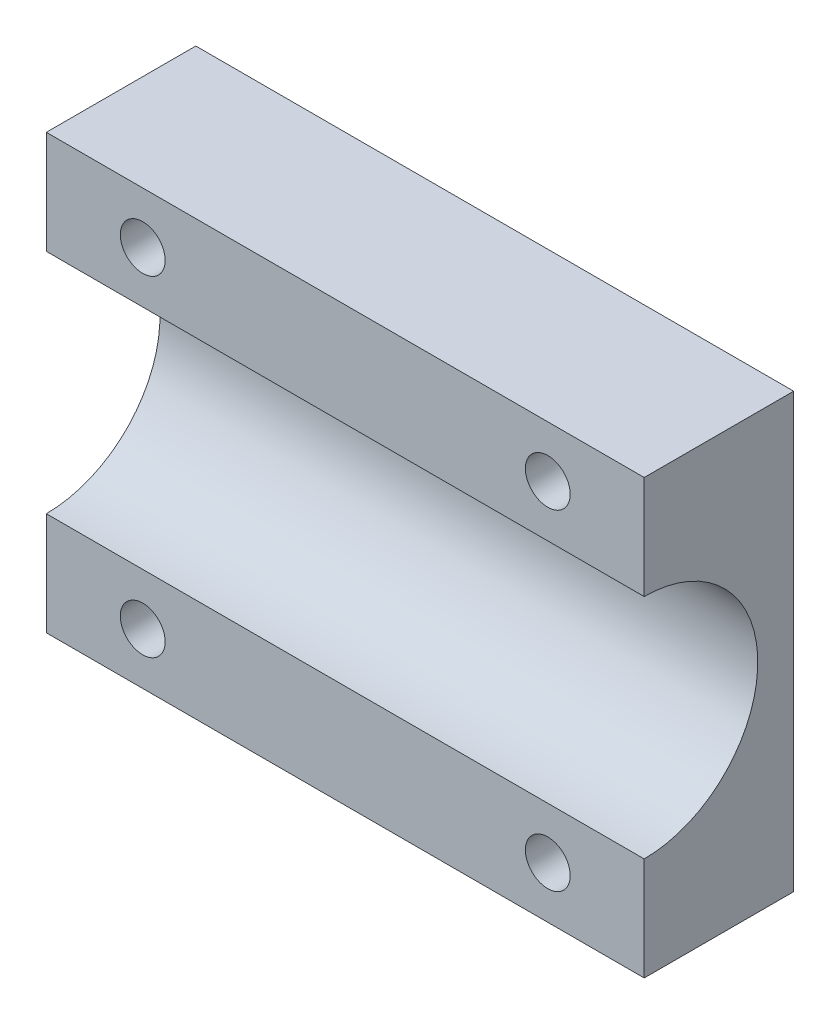
SolidWorks part; units mm, degrees
ref_plane "Front Plane" through (0, 0, 0) normal (1, 0, 0) x (0, 1, 0)
ref_plane "Top Plane" through (0, 0, 0) normal (0, 0, 1) x (0, 1, 0)
ref_plane "Right Plane" through (0, 0, 0) normal (0, 1, 0) x (-1, 0, 0)
sketch "Sketch1" plane through (0, 0, 0) normal (0, 0, 1) x (0, 1, 0)
  line L1 (0, 0) -> (29, 0)
  line L2 (0, 0) -> (0, -40)
  line L3 (0, -40) -> (29, -40)
  line L4 (29, 0) -> (29, -40)
  dimension "D1" = 29
  dimension "D2" = 40
extrude "Boss-Extrude1" add sketch "Sketch1" along normal blind 10 contours L4 L1 L2 L3 region at (20, 14.5, 0)
sketch "Sketch2" plane through (40, 0, 0) normal (1, 0, 0) x (0, 1, 0)
  line L0 (0, 10) -> (29, 10) construction
  circle A0 centre (14.5, 10) radius 7.6
  dimension "D1" = 15.2
extrude "Cut-Extrude1" cut sketch "Sketch2" against normal up to surface (40 mm away) up to face at (0, 14.5, 5)
sketch "Sketch3" plane through (0, 0, 10) normal (0, 0, 1) x (1, 0, 0)
  line L0 (0, 29) -> (12.9, 22.1) construction
  line L1 (40, 22.1) -> (0, 22.1) construction
  line L2 (0, 22.1) -> (12.9, 29) construction
  line L3 (0, 29) -> (40, 29) construction
  line L4 (40, 29) -> (27.1, 22.1) construction
  line L5 (40, 22.1) -> (27.1, 29) construction
  line L6 (0, 6.9) -> (12.9, 0) construction
  line L7 (0, 0) -> (40, 0) construction
  line L8 (0, 0) -> (12.9, 6.9) construction
  line L9 (0, 6.9) -> (40, 6.9) construction
  line L10 (40, 0) -> (27.1, 6.9) construction
  line L11 (40, 6.9) -> (27.1, 0) construction
  circle A0 centre (6.45, 25.55) radius 1.5
  circle A1 centre (33.55, 25.55) radius 1.5
  circle A2 centre (33.55, 3.45) radius 1.5
  circle A3 centre (6.45, 3.45) radius 1.5
  dimension "D2" = 12.9
  dimension "D3" = 12.9
extrude "Cut-Extrude2" cut sketch "Sketch3" against normal up to surface (10 mm away) up to face at (20, 14.5, 0)
equation "\"screw_hole\"= 3mm"
equation "\"offset\"= 2.52mm"
equation "\"y_length\" = 40mm"
equation "\"z_breadth\"= 29mm"
equation "\"D1@Sketch1\"=\"z_breadth\""
equation "\"D2@Sketch1\"=\"y_length\""
equation "\"lm8uu_bearing_dia\"= 15.2mm"
equation "\"D1@Sketch2\"=\"lm8uu_bearing_dia\""
equation "\"D1@Sketch3\"=\"screw_hole\""
equation "\"D3@Sketch3\"=\"D2@Sketch3\""
